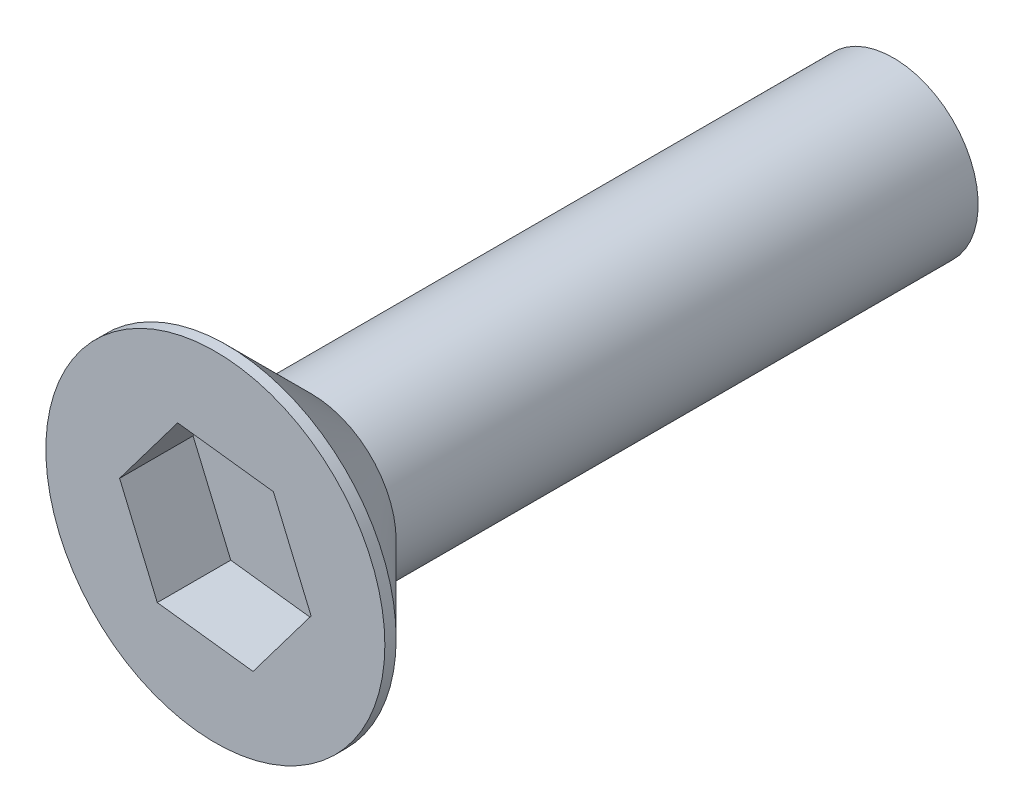
SolidWorks part; units mm, degrees
ref_plane "Front Plane" through (0, 0, 0) normal (0, 0, 1) x (1, 0, 0)
ref_plane "Top Plane" through (0, 0, 0) normal (0, 1, 0) x (1, 0, 0)
ref_plane "Right Plane" through (0, 0, 0) normal (1, 0, 0) x (0, 0, -1)
sketch "Sketch1" plane through (0, 0, 0) normal (0, 0, 1) x (1, 0, 0)
  circle A0 centre (0, 0) radius 1.5
  dimension "D1" = 3
extrude "Boss-Extrude1" add sketch "Sketch1" along normal blind 10.3
sketch "Sketch2" plane through (0, 0, 10.3) normal (0, 0, 1) x (1, 0, 0)
  circle A0 centre (0, 0) radius 3
  dimension "D1" = 6
extrude "Boss-Extrude2" add sketch "Sketch2" along normal blind 1.7
chamfer "Chamfer1" distance 1.5 angle 45 1 edges at (3, 0, 10.3)
sketch "Sketch7" plane through (0, 0, 12) normal (0, 0, 1) x (1, 0, 0)
  line L1 (0.6672, -1.5714) -> (1.6945, -0.2079)
  line L2 (1.6945, -0.2079) -> (1.0273, 1.3635)
  line L3 (1.0273, 1.3635) -> (-0.6672, 1.5714)
  line L4 (-0.6672, 1.5714) -> (-1.6945, 0.2079)
  line L5 (-1.6945, 0.2079) -> (-1.0273, -1.3635)
  line L6 (-1.0273, -1.3635) -> (0.6672, -1.5714)
  circle A0 centre (0, 0) radius 1.4785 construction
extrude "Cut-Extrude1" cut sketch "Sketch7" against normal blind 1.3
